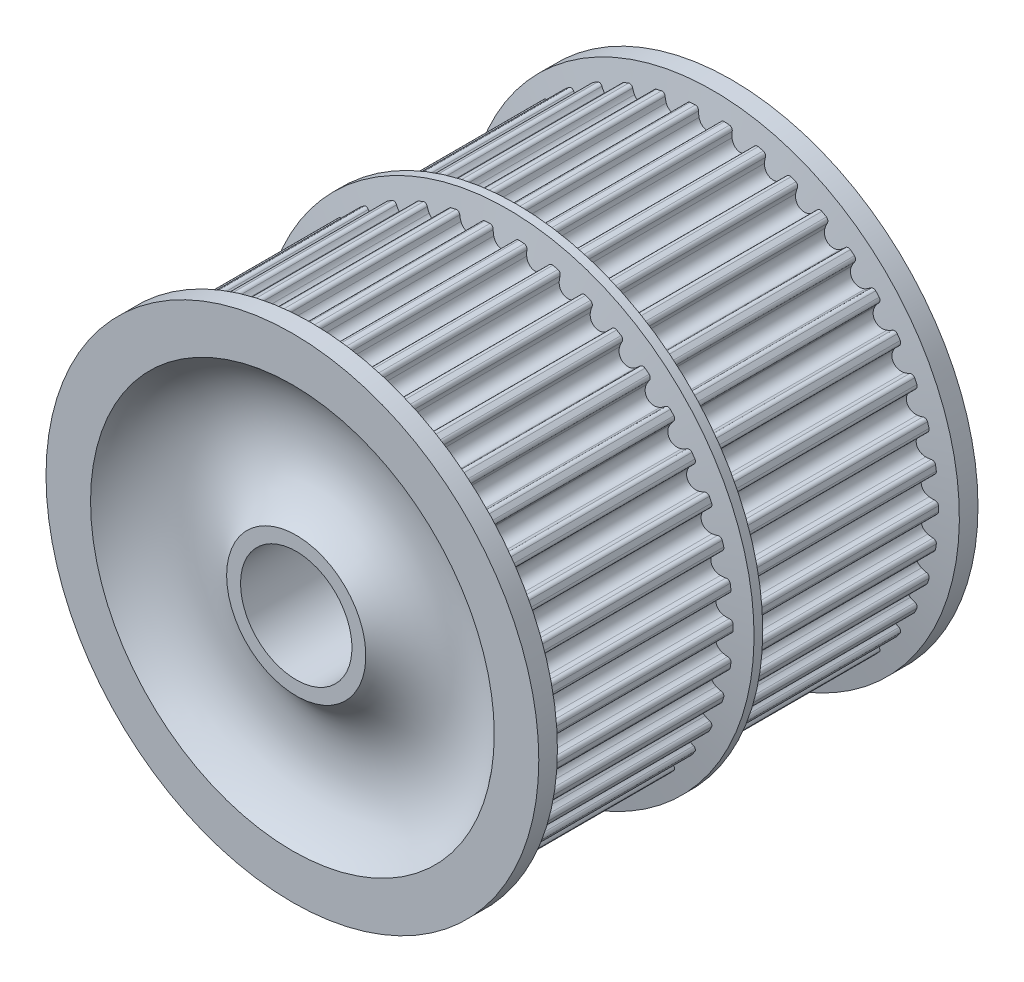
SolidWorks part; units mm, degrees
material "ABS"
ref_plane "Front" through (0, 0, 0) normal (0, 0, 1) x (1, 0, 0)
ref_plane "Top" through (0, 0, 0) normal (0, 1, 0) x (1, 0, 0)
ref_plane "Right" through (0, 0, 0) normal (1, 0, 0) x (0, 0, -1)
ref_axis "side-side" through (80.9, 0, 0) along (-1, 0, 0)
ref_axis "up-down" through (0, 50, 0) along (0, -1, 0)
ref_axis "front-back" through (0, 0, -80.9) along (0, 0, 1)
sketch "Sketch1" plane through (0, 0, 0) normal (0, 0, 1) x (1, 0, 0)
  circle A0 centre (0, 0) radius 35.5
  circle A1 centre (0, 0) radius 8
  dimension "D1" = 71
  dimension "D2" = 16
extrude "Boss-Extrude1" add sketch "Sketch1" along normal mid plane 63.1
shell "Shell1" [suppressed] thickness 3.5
sketch "Sketch3" plane through (0, 0, 0) normal (1, 0, 0) x (0, 0, -1)
  line L0 (-31.55, 35.5) -> (-31.55, -35.5) construction
  line L1 (-31, 0) -> (-31.55, 0)
  line L2 (-31, 0) -> (-31, 10)
  line L3 (-31, 10) -> (-31.55, 10) construction
  line L4 (-31.55, 0) -> (-31.55, 10)
  line L5 (31.55, -35.5) -> (31.55, 35.5) construction
  line L6 (31.55, 0) -> (31, 0)
  line L7 (31.55, 0) -> (31.55, 10)
  line L8 (31.55, 10) -> (31, 10) construction
  line L9 (31, 0) -> (31, 10)
  line L10 (0, 0) -> (-18.4486, 0) construction
  line L11 (31.55, 29) -> (31.55, 10)
  line L16 (26.55, 19.2916) -> (26.55, 7.761) construction
  line L17 (-31.55, 10) -> (-31.55, 29)
  arc A0 (31.55, 29) -> (31, 10) centre (38.4754, 19.2916) ccw
  arc A1 (-31, 10) -> (-31.55, 29) centre (-38.4754, 19.2916) ccw
  dimension "D1" = 10
  dimension "D2" = 0.55
  dimension "D3" = 58
  dimension "D4" = 5
revolve "Cut-Revolve1" cut sketch "Sketch3" angle 360 about L10
sketch "Sketch5" plane through (0, 0, 0) normal (0, 0, 1) x (1, 0, 0)
  line L0 (0, 32.2846) -> (0, 33.4226) construction
  line L1 (-2.0062, 32.7871) -> (2.0062, 32.7871) construction
  circle A0 centre (0, 0) radius 33.4226
  circle A1 centre (0, 0) radius 35.3026 construction
  circle A2 centre (0, 0) radius 30.8799 construction
  arc A7 (2.7729, 32.7312) -> (2.0062, 32.7871) centre (0, 0) ccw
  arc A8 (2.0062, 32.7871) -> (1.4735, 32.3599) centre (1.9751, 32.2801) ccw
  arc A9 (1.2885, 31.7254) -> (1.4735, 32.3599) centre (-1.127, 32.7736) ccw
  arc A10 (-2.0062, 32.7871) -> (-2.7729, 32.7312) centre (0, 0) ccw
  arc A11 (-1.4735, 32.3599) -> (-2.0062, 32.7871) centre (-1.9751, 32.2801) ccw
  arc A12 (-1.4735, 32.3599) -> (-1.2885, 31.7254) centre (1.127, 32.7736) ccw
  arc A13 (-1.2885, 31.7254) -> (1.2885, 31.7254) centre (0, 32.2846) ccw
  dimension "D1" = 66.8451
  dimension "D2" = 0.5741
  dimension "D3" = 1.4046
  dimension "D5" = 0.508
  dimension "D9" = 1.88
  dimension "D10" = 70.6051
  dimension "D4" = 1.138
  dimension "D6" = 133.08
  dimension "D7" = 4.0124
  dimension "D8" = 2.0062
sketch "Sketch6" plane through (0, 0, 0) normal (0, 0, 1) x (1, 0, 0)
  line L0 (-4, 32.604) -> (-4.5129, 36.7846)
  line L1 (-4.5129, 36.7846) -> (4.5129, 36.7846)
  line L2 (4.5129, 36.7846) -> (4, 32.604)
  arc A0 (-2.0062, 32.7871) -> (-2.7729, 32.7312) centre (0, 0) ccw construction
  arc A1 (4, 32.604) -> (2.0843, 32.7823) centre (0, 0) ccw
  arc A2 (-2.0843, 32.7823) -> (-4, 32.604) centre (0, 0) ccw
  arc A5 (1.5426, 32.3489) -> (2.0843, 32.7823) centre (2.0516, 32.2679) cw
  arc A6 (-1.5426, 32.3489) -> (-2.0843, 32.7823) centre (-2.0516, 32.2679) ccw
  arc A8 (1.3527, 31.6975) -> (1.5426, 32.3489) centre (-1.127, 32.7736) ccw
  arc A9 (-1.5426, 32.3489) -> (-1.3527, 31.6975) centre (1.127, 32.7736) ccw
  arc A10 (-1.3527, 31.6975) -> (1.3527, 31.6975) centre (0, 32.2846) ccw
  arc A11 (1.3527, 31.6975) -> (1.5426, 32.3489) centre (-1.127, 32.7736) ccw
  arc A12 (-1.5426, 32.3489) -> (-1.3527, 31.6975) centre (1.127, 32.7736) ccw
  arc A13 (-1.3527, 31.6975) -> (1.3527, 31.6975) centre (0, 32.2846) ccw
  dimension "D2" = 8
  dimension "D3" = 4.5
  dimension "D1" = 0.07
extrude "Cut-Extrude1" cut sketch "Sketch6" against normal through all both and the other way through all from offset 1.5 offset against normal yes
pattern_circular "CirPattern1" count 42 over 360 about axis through (0, 0, -80.9) along (0, 0, 1) of "Cut-Extrude1"
sketch "Sketch7" plane through (0, 0, 0) normal (1, 0, 0) x (0, 0, -1)
  line L0 (0, 32.2846) -> (0, 33.4226) construction
  line L1 (31.55, 30.4401) -> (-31.55, 30.4401) construction
  line L2 (1.5, 30.4401) -> (-1.5, 30.4401)
  line L3 (0, 35.4) -> (0, 37.6453) construction
  line L4 (-1.5, 30.4401) -> (-0.6254, 35.4)
  line L5 (-0.6254, 35.4) -> (0.6254, 35.4)
  line L6 (0.6254, 35.4) -> (1.5, 30.4401)
  line L7 (0, 50) -> (0, -50) construction
  line L8 (80.9, 0) -> (-80.9, 0) construction
  line L10 (31.55, 35.4) -> (28.8746, 35.4)
  line L11 (31.55, 35.4) -> (31.55, 30.4401)
  line L12 (31.55, 30.4401) -> (28, 30.4401)
  line L13 (28.8746, 35.4) -> (28, 30.4401)
  line L14 (-31.55, 30.4401) -> (-28, 30.4401)
  line L15 (-28.8746, 35.4) -> (-28, 30.4401)
  line L16 (-31.55, 35.4) -> (-31.55, 30.4401)
  line L17 (-31.55, 35.4) -> (-28.8746, 35.4)
  line L18 (-7.217, 0) -> (65.2431, 0) construction
  line L19 (31.55, -29) -> (31.55, 29) construction
  point P4 (0, 30.4401)
  dimension "D1" = 3
  dimension "D2" = 80
  dimension "D3" = 35.4
  dimension "D4" = 26.5
revolve "Revolve1" add sketch "Sketch7" angle 360 about L18
